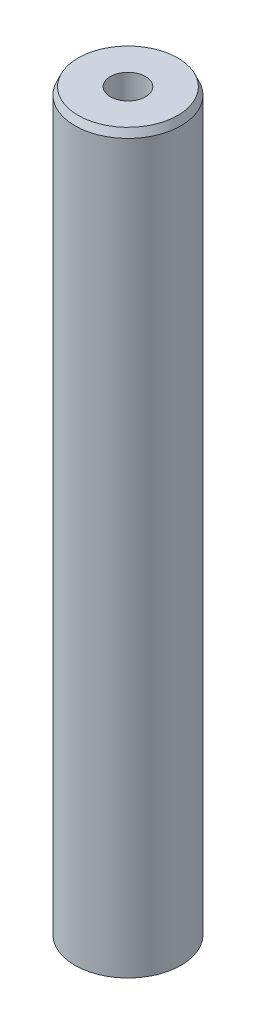
SolidWorks part; units mm, degrees
ref_plane "Front Plane" through (0, 0, 0) normal (0, 0, 1) x (1, 0, 0)
ref_plane "Top Plane" through (0, 0, 0) normal (0, 1, 0) x (1, 0, 0)
ref_plane "Right Plane" through (0, 0, 0) normal (1, 0, 0) x (0, 0, -1)
sketch "Sketch1" plane through (0, 0, 0) normal (0, 1, 0) x (1, 0, 0)
  circle A0 centre (0, 0) radius 35
  dimension "SHAFT_OD" = 70
extrude "Boss-Extrude1" add sketch "Sketch1" along normal blind 486.4249
sketch "Sketch2" plane through (0, 0, 0) normal (0, 1, 0) x (1, 0, 0)
  circle A0 centre (0, 0) radius 11.5967
  dimension "BORE_D" = 23.1935
extrude "Cut-Extrude1" cut sketch "Sketch2" along normal through all
chamfer "Chamfer1" distance 4.8287 angle 24.102 2 edges at (0, 486.4249, 35) (0, 0, 35) first distance on face at (0, 486.4249, 35) first distance on face at (0, 0, 11.5967)
